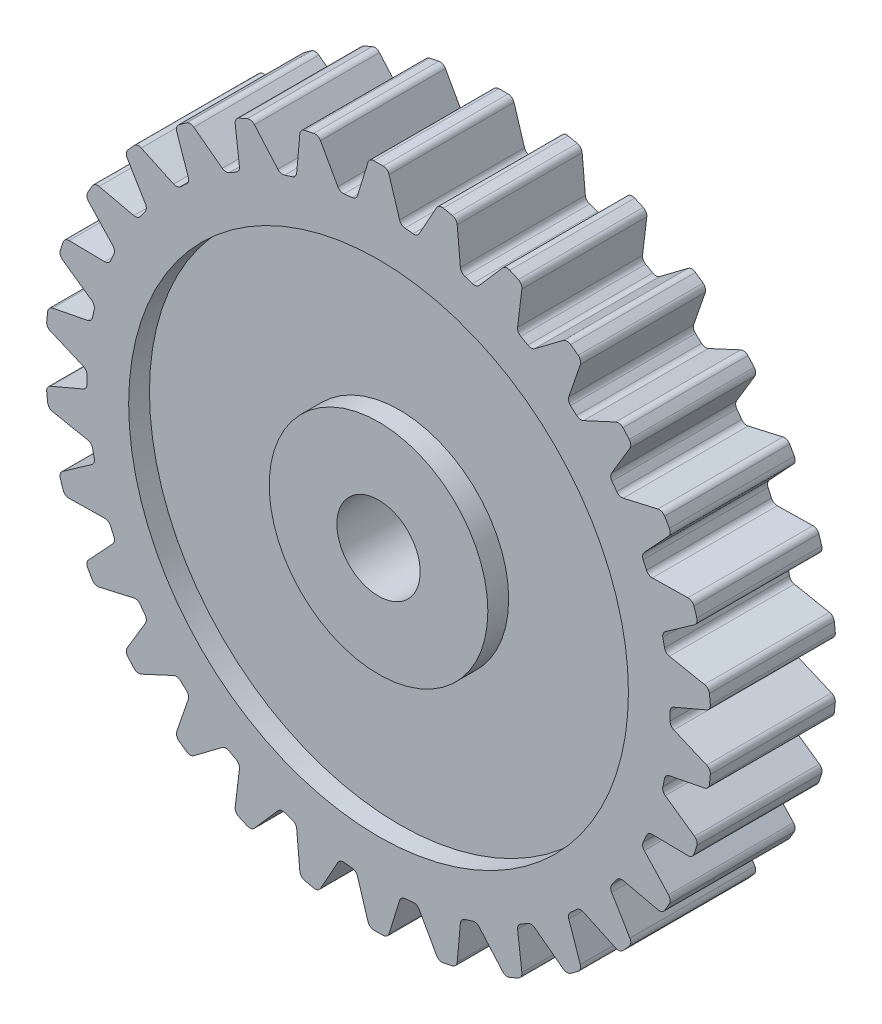
SolidWorks part; units mm, degrees
ref_plane "Front Plane" through (0, 0, 0) normal (0, 0, 1) x (1, 0, 0)
ref_plane "Top Plane" through (0, 0, 0) normal (0, 1, 0) x (1, 0, 0)
ref_plane "Right Plane" through (0, 0, 0) normal (1, 0, 0) x (0, 0, -1)
sketch "Sketch1" plane through (0, 0, 0) normal (0, 0, 1) x (1, 0, 0)
  circle A2 centre (0, 0) radius 14
  dimension "Blank diameter" = 28
extrude "Body" add sketch "Sketch1" against normal blind 6
sketch "Sketch2" plane through (0, 0, 0) normal (0, 0, 1) x (1, 0, 0)
  line L0 (0, 26.3446) -> (0, 3.6554) construction
  line L1 (-0.755, 14.981) -> (-1.0697, 13.9591)
  line L2 (-0.755, 14.981) -> (-0.4431, 15.9939)
  line L3 (0.755, 14.981) -> (1.0697, 13.9591)
  line L4 (0.755, 14.981) -> (0.4431, 15.9939)
  line L5 (0, 0) -> (-2.2254, 44.1563) construction
  line L6 (0, 0) -> (2.1494, 42.6484) construction
  arc A0 (0.4431, 15.9939) -> (-0.4431, 15.9939) centre (0, 0) ccw
  arc A1 (0.755, 14.981) -> (-0.755, 14.981) centre (0, 0) ccw construction
  arc A2 (1.0697, 13.9591) -> (-1.0697, 13.9591) centre (0, 0) ccw
  point P1 (0, 15)
  dimension "D2" = 20
  dimension "D3" = 20
  dimension "Full diameter" = 32
  dimension "Pitch diameter" = 30
  dimension "Blank diameter" = 28
  dimension "Tooth width PCD" = 1.51
extrude "Tooth" add sketch "Sketch2" against normal blind 6
fillet "Tooth Fillet" radius 0.3 4 edges at (-0.4431, 15.9939, -3) (-1.0697, 13.9591, -3) (0.4431, 15.9939, -3) (1.0697, 13.9591, -3)
pattern_circular "Tooth Pattern" count 30 over 360 about axis through (0, 0, 0) along (0, 0, 1) of "Tooth", "Tooth Fillet"
ref_axis "Axis1" through (0, 0, 0) along (0, 0, -1)
sketch "Sketch3" plane through (0, 0, 0) normal (0, 0, 1) x (1, 0, 0)
  circle A0 centre (0, 0) radius 5.25
  circle A1 centre (0, 0) radius 12
  dimension "Plastic boss" = 10.5
  dimension "Resses" = 24
extrude "Resses1" cut sketch "Sketch3" against normal blind 1
sketch "Sketch4" plane through (0, 0, -6) normal (0, 0, -1) x (-1, 0, 0)
  circle A0 centre (0, 0) radius 12
  circle A1 centre (0, 0) radius 5.25
  dimension "Plastic boss" = 10.5
  dimension "Resses" = 24
extrude "Resses2" cut sketch "Sketch4" against normal blind 1
sketch "Sketch5" plane through (0, 0, -6) normal (0, 0, -1) x (-1, 0, 0)
  circle A0 centre (0, 0) radius 5
  dimension "D1" = 10
extrude "Brass boss" add sketch "Sketch5" along normal blind 5.7
sketch "Sketch6" plane through (0, 0, -11.7) normal (0, 0, -1) x (-1, 0, 0)
  circle A0 centre (0, 0) radius 2
  dimension "D1" = 4
extrude "Bore" cut sketch "Sketch6" against normal through all
sketch "Sketch7" plane through (0, 0, 0) normal (0, 1, 0) x (1, 0, 0)
  circle A0 centre (0, 8.8626) radius 1
  dimension "D1" = 2
extrude "Grub screw" cut sketch "Sketch7" against normal through all
sketch "Sketch8" plane through (0, 0, -5) normal (0, 0, -1) x (-1, 0, 0)
  circle A0 centre (-0.8321, 10.5608) radius 1.8434
extrude "Extrude1" [suppressed] add sketch "Sketch8" along normal blind 5
